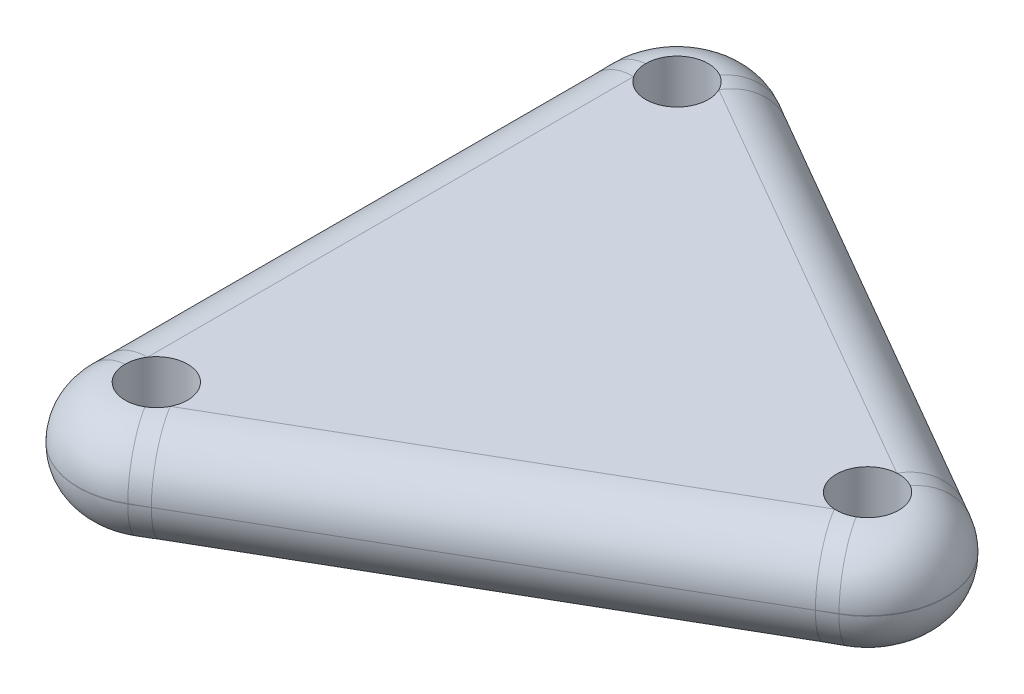
SolidWorks part; units mm, degrees
material "ABS PC"
ref_plane "Alzado" through (0, 0, 0) normal (1, 0, 0) x (0, 1, 0)
ref_plane "Planta" through (0, 0, 0) normal (0, 0, 1) x (0, 1, 0)
ref_plane "Vista lateral" through (0, 0, 0) normal (0, 1, 0) x (-1, 0, 0)
sketch "Croquis2" plane through (0, 0, 0) normal (0, 1, 0) x (-1, 0, 0)
  line L0 (0, 50) -> (0, 0) construction
  line L1 (0, 0) -> (-43.3013, 25) construction
  line L5 (-7.5, 12.9904) -> (3.75, -6.4952) construction
  line L6 (7.5, 50) -> (7.5, 0)
  line L8 (-7.5, 25.9808) -> (-7.5, 50) construction
  line L9 (-39.5513, 31.4952) -> (-47.0513, 18.5048) construction
  line L10 (-47.0513, 18.5048) -> (-3.75, -6.4952)
  line L11 (-18.75, 19.4856) -> (-39.5513, 31.4952) construction
  line L12 (-3.75, 56.4952) -> (-47.0513, 31.4952)
  circle A0 centre (0, 0) radius 3
  circle A1 centre (-43.3013, 25) radius 3
  circle A2 centre (0, 50) radius 3
  arc A5 (7.5, 50) -> (-7.5, 50) centre (0, 50) ccw construction
  arc A9 (-47.0513, 18.5048) -> (-39.5513, 31.4952) centre (-43.3013, 25) cw construction
  arc A10 (7.5, 0) -> (-3.75, -6.4952) centre (0, 0) cw
  arc A11 (-18.75, 19.4856) -> (-7.5, 25.9808) centre (-15, 25.9808) ccw construction
  arc A12 (-47.0513, 18.5048) -> (-47.0513, 31.4952) centre (-43.3013, 25) cw
  arc A13 (7.5, 50) -> (-3.75, 56.4952) centre (0, 50) ccw
  point P39 (3.75, -6.4952)
  dimension "D3" = 6
  dimension "D5" = 7.5
  dimension "D1" = 50
  dimension "D2" = 60
  dimension "D4" = 15
extrude "Saliente-Extruir1" add sketch "Croquis2" along normal mid plane 10
fillet "Redondeo1" radius 5 12 edges at (-3.75, 5, 56.4952) (-7.5, 5, 25) (-3.75, 5, -6.4952) (25.4006, 5, 6.0048) (50.8013, 5, 25) (-3.75, -5, 56.4952) (-7.5, -5, 25) (-3.75, -5, -6.4952) (25.4006, -5, 6.0048) (50.8013, -5, 25) (25.4006, 5, 43.9952) (25.4006, -5, 43.9952)
equation "\"Zbarras\"= 50"
equation "\"D1@Croquis2\"=\"Zbarras\""
equation "\"angulo\"= 60"
equation "\"ancho\"= 15"
equation "\"esp\"= 10"
equation "\"D2@Croquis2\"=\"angulo\""
equation "\"D4@Croquis2\"=\"ancho\""
equation "\"D1@Saliente-Extruir1\"=\"esp\""
equation "\"agujeros\"= 6"
equation "\"D3@Croquis2\"=\"agujeros\""
equation "\"D5@Croquis2\"=\"D4@Croquis2\"*(1-cos(\"D2@Croquis2\"))"
equation "\"D1@Redondeo1\"=\"esp\"/2"
